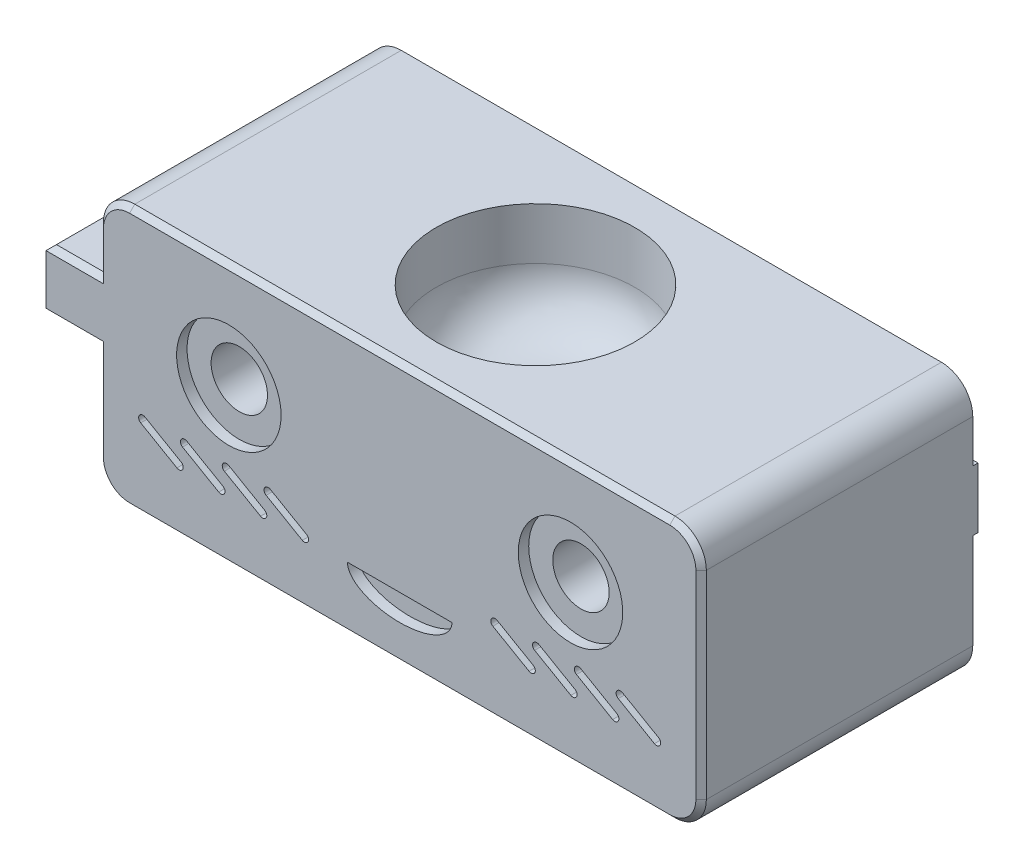
SolidWorks part; units mm, degrees
ref_plane "前视基准面" through (0, 0, 0) normal (0, 0, 1) x (1, 0, 0)
ref_plane "上视基准面" through (0, 0, 0) normal (0, 1, 0) x (1, 0, 0)
ref_plane "右视基准面" through (0, 0, 0) normal (1, 0, 0) x (0, 0, -1)
sketch "草图1" plane through (0, 0, 0) normal (0, 0, 1) x (1, 0, 0)
  line L0 (0, 0) -> (20.4762, 0) construction
  line L1 (0, 2.9) -> (42.0238, 2.9) construction
  line L2 (0, 10) -> (49.0146, 10) construction
  line L3 (-5.1974, -2.9) -> (42.0238, -2.9) construction
  line L4 (0, -10) -> (49.0146, -10) construction
  dimension "D1" = 2.9
  dimension "D2" = 10
sketch "草图3" plane through (0, 0, 0) normal (0, 0, 1) x (1, 0, 0)
  line L0 (0, 0) -> (0, 10) construction
  line L1 (-200000, 10) -> (200049.0146, 10) construction
  line L2 (0, 0) -> (-28.85, 0) construction
  line L3 (-200000, 0) -> (200020.4762, 0) construction
  line L4 (25.85, 10) -> (-25.85, 10)
  line L5 (-28.85, 7) -> (-28.85, 0)
  line L6 (-28.85, 0) -> (-28.85, -12)
  line L7 (-25.85, -15) -> (25.85, -15)
  line L8 (0, 0) -> (0, -15) construction
  line L9 (28.85, 0) -> (28.85, -12)
  line L10 (28.85, 7) -> (28.85, 0)
  circle A0 centre (-16.35, 0) radius 2.7
  arc A1 (-28.85, -12) -> (-25.85, -15) centre (-25.85, -12) ccw
  arc A2 (-25.85, 10) -> (-28.85, 7) centre (-25.85, 7) ccw
  circle A3 centre (16.35, 0) radius 2.7
  arc A4 (28.85, -12) -> (25.85, -15) centre (25.85, -12) cw
  arc A5 (25.85, 10) -> (28.85, 7) centre (25.85, 7) cw
  point P15 (-28.85, -15)
  point P18 (-28.85, 10)
  dimension "D3" = 5.4
  dimension "D5" = 3
  dimension "D1" = 28.85
  dimension "D2" = 15
  dimension "D4" = 12.5
extrude "凸台-拉伸2" add sketch "草图3" along normal blind 26
ref_plane "基准面1" through (0, 0, 26) normal (0, 0, 1) x (1, 0, 0)
sketch "草图5" plane through (0, 0, 26) normal (0, 0, 1) x (1, 0, 0)
  line L0 (0, 0) -> (0, 10) construction
  line L1 (-200000, 10) -> (200049.0146, 10) construction
  circle A10 centre (-16.35, 0) radius 2.7 construction
  circle A11 centre (-16.35, 0) radius 2.7 construction
  circle A12 centre (-16.35, 0) radius 5
  circle A13 centre (16.35, 0) radius 5
  dimension "D1" = 10
extrude "切除-拉伸1" cut sketch "草图5" against normal blind 1
sketch "草图6" plane through (0, 0, 26) normal (0, 0, 1) x (1, 0, 0)
  line L0 (0, 0) -> (0, -15) construction
  line L1 (-25.85, -15) -> (25.85, -15) construction
  line L2 (5, -9.0003) -> (-5, -9.0003)
  line L3 (-21.1179, -9) -> (-24.5821, -7) construction
  line L4 (-28.85, 0) -> (-22.85, 0) construction
  line L5 (-21.3179, -9.3464) -> (-24.7821, -7.3464)
  line L6 (-20.9179, -8.6536) -> (-24.3821, -6.6536)
  line L7 (-200000, -10) -> (200049.0146, -10) construction
  line L8 (-17.1179, -9) -> (-20.5821, -7) construction
  line L11 (-17.3179, -9.3464) -> (-20.7821, -7.3464)
  line L14 (-16.9179, -8.6536) -> (-20.3821, -6.6536)
  line L17 (-13.1179, -9) -> (-16.5821, -7) construction
  line L20 (-13.3179, -9.3464) -> (-16.7821, -7.3464)
  line L23 (-12.9179, -8.6536) -> (-16.3821, -6.6536)
  line L26 (-9.1179, -9) -> (-12.5821, -7) construction
  line L29 (-200000, 0) -> (200020.4762, 0) construction
  line L30 (-22.85, 0) -> (-22.85, -8) construction
  line L31 (-28.85, 7) -> (-28.85, -12) construction
  line L32 (-9.3179, -9.3464) -> (-12.7821, -7.3464)
  line L33 (-8.9179, -8.6536) -> (-12.3821, -6.6536)
  line L34 (12.5821, -9) -> (9.1179, -7) construction
  line L35 (12.3821, -9.3464) -> (8.9179, -7.3464)
  line L36 (12.7821, -8.6536) -> (9.3179, -6.6536)
  line L37 (16.5821, -9) -> (13.1179, -7) construction
  line L38 (16.3821, -9.3464) -> (12.9179, -7.3464)
  line L39 (16.7821, -8.6536) -> (13.3179, -6.6536)
  line L40 (20.5821, -9) -> (17.1179, -7) construction
  line L41 (20.3821, -9.3464) -> (16.9179, -7.3464)
  line L42 (20.7821, -8.6536) -> (17.3179, -6.6536)
  line L43 (24.5821, -9) -> (21.1179, -7) construction
  line L44 (24.3821, -9.3464) -> (20.9179, -7.3464)
  line L45 (24.7821, -8.6536) -> (21.3179, -6.6536)
  circle A0 centre (-16.35, 0) radius 5 construction
  circle A1 centre (-16.35, 0) radius 5 construction
  arc A2 (-21.3179, -9.3464) -> (-20.9179, -8.6536) centre (-21.1179, -9) ccw
  arc A3 (-24.3821, -6.6536) -> (-24.7821, -7.3464) centre (-24.5821, -7) ccw
  arc A18 (-17.3179, -9.3464) -> (-16.9179, -8.6536) centre (-17.1179, -9) ccw
  arc A19 (-20.3821, -6.6536) -> (-20.7821, -7.3464) centre (-20.5821, -7) ccw
  arc A20 (-13.3179, -9.3464) -> (-12.9179, -8.6536) centre (-13.1179, -9) ccw
  arc A21 (-16.3821, -6.6536) -> (-16.7821, -7.3464) centre (-16.5821, -7) ccw
  arc A22 (-9.3179, -9.3464) -> (-8.9179, -8.6536) centre (-9.1179, -9) ccw
  arc A23 (-12.3821, -6.6536) -> (-12.7821, -7.3464) centre (-12.5821, -7) ccw
  arc A24 (12.3821, -9.3464) -> (12.7821, -8.6536) centre (12.5821, -9) ccw
  arc A25 (9.3179, -6.6536) -> (8.9179, -7.3464) centre (9.1179, -7) ccw
  arc A26 (16.3821, -9.3464) -> (16.7821, -8.6536) centre (16.5821, -9) ccw
  arc A27 (13.3179, -6.6536) -> (12.9179, -7.3464) centre (13.1179, -7) ccw
  arc A28 (20.3821, -9.3464) -> (20.7821, -8.6536) centre (20.5821, -9) ccw
  arc A29 (17.3179, -6.6536) -> (16.9179, -7.3464) centre (17.1179, -7) ccw
  arc A30 (24.3821, -9.3464) -> (24.7821, -8.6536) centre (24.5821, -9) ccw
  arc A31 (21.3179, -6.6536) -> (20.9179, -7.3464) centre (21.1179, -7) ccw
  ellipse E0 centre (0, -9.0003) end of major axis (5, -9.0003) minor radius 2.5 (5, -9.0003) -> (-5, -9.0003) cw
  point P14 (0, -11.5003)
  point P19 (-22.85, -8)
  point P29 (-18.85, -8)
  point P36 (-14.85, -8)
  point P44 (-10.85, -8)
  point P52 (10.85, -8)
  point P59 (14.85, -8)
  point P66 (18.85, -8)
  point P73 (22.85, -8)
  dimension "D6" = 0.8
  dimension "D1" = 5
  dimension "D2" = 2.5
  dimension "D3" = 6
  dimension "D4" = 30
  dimension "D5" = 4
  dimension "D7" = 2
extrude "切除-拉伸2" cut sketch "草图6" against normal blind 1
sketch "草图7" plane through (0, 0, 0) normal (1, 0, 0) x (0, 0, -1)
  line L0 (0, -12) -> (0, 7) construction
  line L1 (0, -12) -> (0, 10) construction
  line L2 (0, 8.4) -> (-1.8, 8.4)
  line L3 (-7.2, 3) -> (-7.2, -6.8)
  line L4 (-7.2, -6.8) -> (-18.2, -6.8)
  line L5 (-18.2, -6.8) -> (-18.2, -15)
  line L6 (-26, -15) -> (0, -15) construction
  line L7 (-26, 10) -> (0, 10) construction
  line L8 (-26, 10) -> (0, 10) construction
  line L9 (0, 7) -> (0, 10) construction
  line L10 (-1.8, 8.4) -> (-7.2, 3)
  line L11 (-18.2, -15) -> (0, -15)
  line L12 (0, -15) -> (0, 8.4)
  point P3 (-7.2, 8.4)
  dimension "D1" = 1.6
  dimension "D2" = 15.2
  dimension "D3" = 7.2
  dimension "D4" = 11
extrude "切除-拉伸3" cut sketch "草图7" against normal mid plane 48
sketch "草图8" plane through (0, 0, 0) normal (0, 0, 1) x (1, 0, 0)
  line L0 (-24, -15) -> (-24, 8.4) construction
  line L1 (-28.85, 7) -> (-28.85, -12) construction
  line L2 (-24, -15) -> (-24, 8.4) construction
  line L3 (-28.85, 7) -> (-28.85, -12) construction
  line L4 (-24, 2.9) -> (-28.85, 2.9)
  line L5 (-200000, 2.9) -> (200042.0238, 2.9) construction
  line L6 (-28.85, 2.9) -> (-28.85, -2.875)
  line L7 (-28.85, -2.875) -> (-24, -2.9)
  line L8 (-200005.1974, -2.9) -> (200042.0238, -2.9) construction
  line L9 (-24, -2.9) -> (-24, 2.9)
  line L10 (0, 0) -> (0, 10) construction
  line L11 (-200000, 10) -> (200049.0146, 10) construction
  line L12 (28.85, -2.875) -> (24, -2.9)
  line L13 (28.85, 2.9) -> (28.85, -2.875)
  line L14 (24, 2.9) -> (28.85, 2.9)
  line L15 (24, -2.9) -> (24, 2.9)
extrude "凸台-拉伸3" add sketch "草图8" against normal blind 1
chamfer "倒角1" distance 0.5 angle 45 8 edges at (-26.425, 2.9, -1) (-28.85, 0.0125, -1) (-26.425, -2.8875, -1) (-24, 0, -1) (26.425, 2.9, -1) (24, 0, -1) (26.425, -2.8875, -1) (28.85, 0.0125, -1)
ref_plane "基准面2" through (-28.85, 0, 0) normal (-1, 0, 0) x (0, 0, 1)
sketch "草图9" plane through (-28.85, 0, 0) normal (-1, 0, 0) x (0, 0, 1)
  line L0 (0, 2.9) -> (26, 2.9) construction
  line L1 (26, -13.2) -> (26, 13.2) construction
  line L2 (0, -2.875) -> (26, -2.875) construction
  line L3 (26, 7) -> (26, -12) construction
  line L4 (26, -2.875) -> (26, 2.9)
  line L5 (26, 2.9) -> (5, 2.9)
  line L6 (5, 2.9) -> (5, -2.875)
  line L7 (5, -2.875) -> (26, -2.875)
  dimension "D1" = 21
extrude "凸台-拉伸4" add sketch "草图9" along normal blind 5
chamfer "倒角3" distance 0.5 angle 45 14 edges at (-31.35, -2.875, 26) (-33.85, -2.875, 15.5) (-33.85, 0.0125, 5) (-33.85, 2.9, 15.5) (-31.35, 2.9, 26) (-28.85, -7.4375, 26) (-27.9713, -14.1213, 26) (0, -15, 26) (27.9713, -14.1213, 26) (28.85, -2.5, 26) (-28.85, 4.95, 26) (27.9713, 9.1213, 26) (-27.9713, 9.1213, 26) (0, 10, 26)
sketch "草图10" plane through (0, 0, 0) normal (1, 0, 0) x (0, 0, -1)
  line L0 (-7.2, -6.8) -> (0, -6.8)
  line L1 (0, -12) -> (0, -2.875) construction
  line L2 (0, -6.8) -> (0, 8.4)
  line L3 (0, 8.4) -> (-1.8, 8.4)
  line L4 (-1.8, 8.4) -> (-7.2, 3)
  line L5 (-7.2, 3) -> (-7.2, -6.8)
extrude "凸台-拉伸5" add sketch "草图10" along normal mid plane 20
chamfer "倒角4" distance 2 angle 45 6 edges at (-10, -1.9, 7.2) (-10, 5.7, 4.5) (-10, 8.4, 0.9) (10, -1.9, 7.2) (10, 8.4, 0.9) (10, 5.7, 4.5)
sketch "草图4" plane through (0, 0, 0) normal (1, 0, 0) x (0, 0, -1)
  line L0 (-25.5, 10) -> (0, 10) construction
  line L1 (-25.5, 10) -> (0, 10) construction
  line L2 (-13, 10) -> (-13, -15)
  line L3 (-25.5, -15) -> (0, -15) construction
  line L4 (-13, -15) -> (-11.4, -15)
  line L5 (-11.4, -15) -> (-11.4, 0)
  line L6 (-11.4, 0) -> (-3.5, 0) construction
  line L7 (-3.5, 0) -> (-3.5, 10) construction
  line L8 (-13, 10) -> (-3.5, 10)
  line L9 (-11.4, 0) -> (-8.8, 0)
  line L11 (-25.5, -15) -> (0, -15) construction
  line L13 (0, -12) -> (0, -2.875) construction
  line L15 (0, -12) -> (0, -2.875) construction
  line L17 (-3.5, 5.0438) -> (-3.5, 10)
  arc A0 (-8.8, 0) -> (-3.5, 5.0438) centre (-8.55, 5.0438) ccw
  dimension "D1" = 1.6
  dimension "D2" = 9.5
  dimension "D3" = 10
  dimension "D4" = 4.2
  dimension "D7" = 13
revolve "切除-旋转1" cut sketch "草图4" angle 360 about L2
